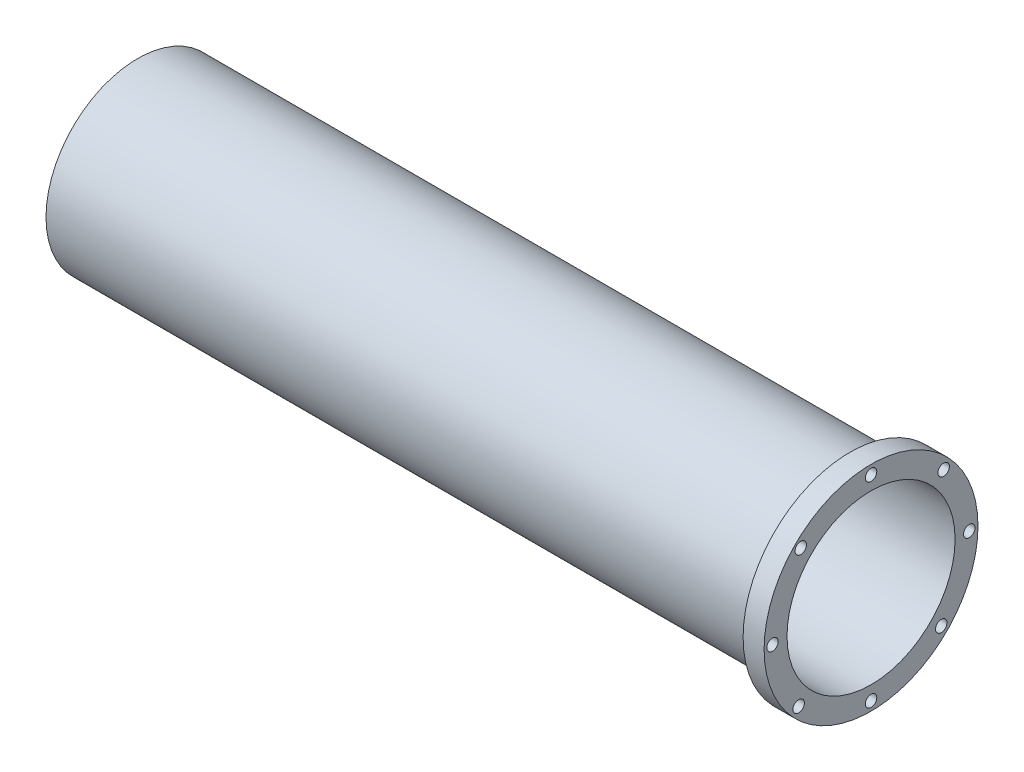
SolidWorks part; units mm, degrees
material "Liga 1060"
ref_plane "Plano frontal" through (0, 0, 0) normal (0, 0, 1) x (1, 0, 0)
ref_plane "Plano superior" through (0, 0, 0) normal (0, 1, 0) x (1, 0, 0)
ref_plane "Plano direito" through (0, 0, 0) normal (1, 0, 0) x (0, 0, -1)
sketch "Esboço4" plane through (0, 0, 0) normal (0, 1, 0) x (1, 0, 0)
  line L1 (-186.5, 60.7488) -> (-186.5, 62.7488)
  line L2 (-186.5, 62.7488) -> (0, 62.7488)
  line L3 (0, 62.7488) -> (0, 66.7488)
  line L4 (0, 66.7488) -> (5.5, 66.7488)
  line L5 (5.5, 66.7488) -> (5.5, 60.7488)
  line L8 (-186.5, 60.7488) -> (-186.5, 38.7488)
  line L9 (-186.5, 38.7488) -> (-183.5, 38.7488)
  line L10 (-183.5, 38.7488) -> (-183.5, 59.0151)
  line L11 (5.5, 60.7488) -> (-181.6823, 60.7488)
  line L12 (-185, 38.7488) -> (5.5, 38.7488) construction
  arc A2 (-181.6823, 60.7488) -> (-183.5, 59.0151) centre (-181.7662, 59.0171) ccw
  dimension "D1" = 6
  dimension "D2" = 22
  dimension "D3" = 2
  dimension "D4" = 3
  dimension "D5" = 5.5
  dimension "D6" = 186.5
revolve "Revolução2" add sketch "Esboço4" angle 360 about L12
sketch "Esboço5" plane through (5.5, 0, 0) normal (1, 0, 0) x (0, 0, -1)
  line L0 (38.7488, 28) -> (38.7488, -28) construction
  line L1 (10.7488, 0) -> (66.7488, 0) construction
  line L2 (66.7488, 0) -> (60.7488, 0) construction
  line L3 (62.7488, 0) -> (66.7488, 0) construction
  line L4 (19.7948, -17.3988) -> (59.405, 18.903) construction
  line L5 (8.3719, 29.9672) -> (58.8261, -19.5167) construction
  circle A0 centre (38.7488, 0) radius 28 construction
  circle A1 centre (20.3425, 18.2269) radius 1.5
  circle A2 centre (38.7488, 25.5941) radius 1.5
  circle A3 centre (57.7552, 17.2634) radius 1.5
  circle A4 centre (64.4684, 0) radius 1.5
  circle A5 centre (57.1247, -17.8481) radius 1.5
  circle A6 centre (38.7488, -25.6381) radius 1.5
  circle A7 centre (19.7948, -17.3988) radius 1.5
  circle A8 centre (12.9478, 0) radius 1.5
extrude "Corte-extrusão5" cut sketch "Esboço5" against normal blind 5
